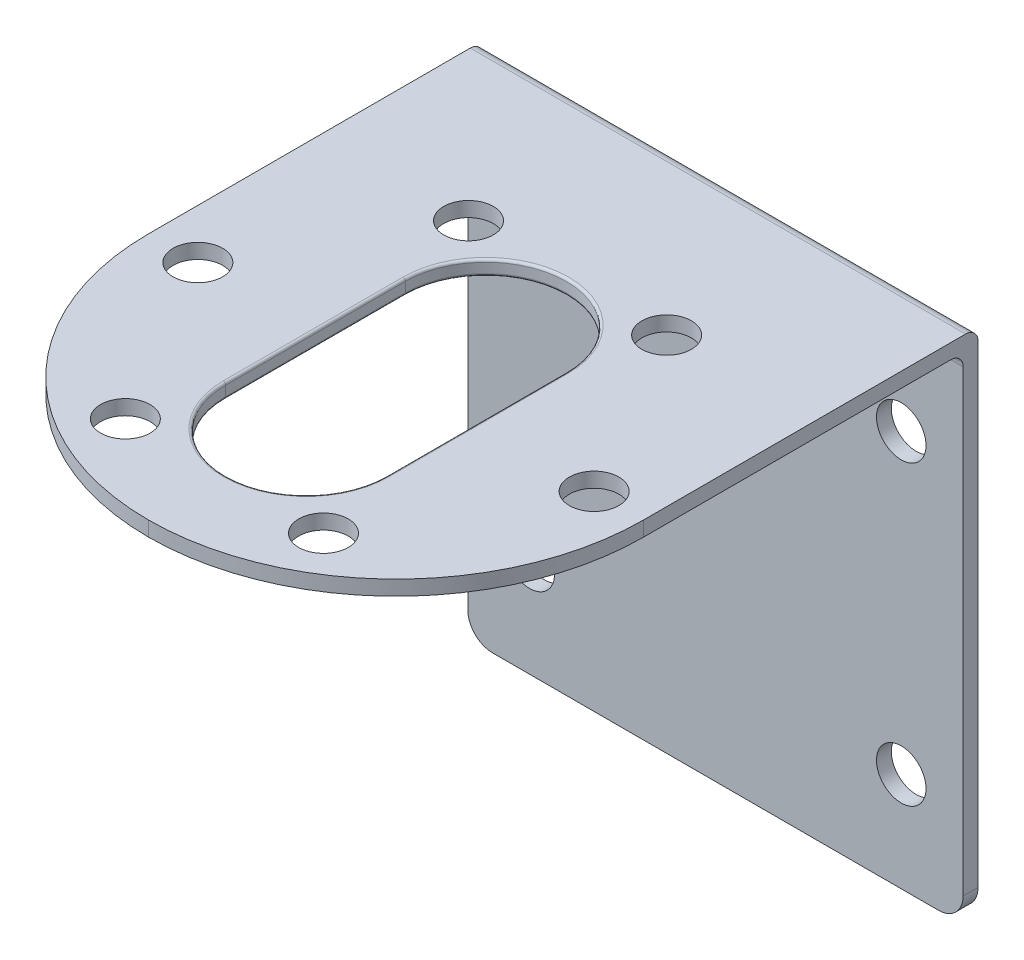
SolidWorks part; units mm, degrees
material "延性铁"
ref_plane "Front" through (0, 0, 0) normal (0, 0, 1) x (1, 0, 0)
ref_plane "Top" through (0, 0, 0) normal (0, 1, 0) x (1, 0, 0)
ref_plane "Right" through (0, 0, 0) normal (1, 0, 0) x (0, 0, -1)
sketch "草图2" plane through (0, 0, 0) normal (0, 0, 1) x (1, 0, 0)
  line L1 (0, 0) -> (40, 0)
  line L2 (0, 0) -> (0, 40)
  line L3 (0, 40) -> (40, 40)
  line L4 (40, 0) -> (40, 40)
  circle A0 centre (5, 32) radius 2
  circle A1 centre (35, 8) radius 2
  circle A2 centre (5, 8) radius 2
  circle A3 centre (35, 32) radius 2
  dimension "D3" = 5
  dimension "D4" = 8
  dimension "D5" = 5
  dimension "D6" = 8
  dimension "D1" = 40
  dimension "D2" = 40
extrude "凸台-拉伸1" add sketch "草图2" along normal blind 1.2
sketch "草图3" plane through (0, 40, 0) normal (0, 1, 0) x (1, 0, 0)
  line L1 (40, 0) -> (0, 0)
  line L2 (40, 0) -> (40, -47)
  line L3 (40, -47) -> (0, -47)
  line L4 (0, 0) -> (0, -47)
  dimension "D1" = 47
extrude "凸台-拉伸2" add sketch "草图3" along normal blind 1.2
fillet "圆角1" radius 1 2 edges at (20, 41.2, 0) (20, 40, 1.2)
fillet "圆角2" radius 20 2 edges at (0, 40.6, 47) (40, 40.6, 47)
fillet "圆角3" radius 2 2 edges at (40, 0, 0.6) (0, 0, 0.6)
sketch "草图4" plane through (0, 41.2, 0) normal (0, 1, 0) x (1, 0, 0)
  line L0 (40, -27) -> (0, -27)
  arc A0 (0, -27) -> (20, -47) centre (20, -27) ccw construction
  circle A1 centre (20, -27) radius 16
  dimension "D1" = 32
sketch "草图5" plane through (0, 41.2, 0) normal (0, 1, 0) x (1, 0, 0)
  line L0 (20, -19.75) -> (20, -34.25) construction
  line L1 (40, -27) -> (0, -27) construction
  line L2 (26.5, -19.75) -> (26.5, -34.25)
  line L3 (13.5, -19.75) -> (13.5, -34.25)
  arc A0 (26.5, -19.75) -> (13.5, -19.75) centre (20, -19.75) ccw
  arc A1 (13.5, -34.25) -> (26.5, -34.25) centre (20, -34.25) ccw
  point P4 (20, -27)
  point P9 (20, -40.75)
  point P10 (20, -13.25)
  dimension "D1" = 13
  dimension "D2" = 27.5
extrude "切除-拉伸1" cut sketch "草图5" against normal through all
sketch "草图7" plane through (0, 41.2, 0) normal (0, 1, 0) x (1, 0, 0)
  line L0 (40, -27) -> (0, -27) construction
  circle A0 centre (36, -27) radius 2
  circle A1 centre (20, -27) radius 16 construction
  circle A2 centre (4, -27) radius 2
  circle A3 centre (28, -40.8564) radius 2
  circle A4 centre (12, -40.8564) radius 2
  circle A5 centre (28, -13.1436) radius 2
  circle A6 centre (12, -13.1436) radius 2
  dimension "D1" = 60
  dimension "D2" = 60
extrude "切除-拉伸3" cut sketch "草图7" against normal through all
fillet "圆角4" radius 0.2 8 edges at (20, 41.2, 40.75) (13.5, 41.2, 27) (20, 41.2, 13.25) (20, 40, 13.25) (13.5, 40, 27) (20, 40, 40.75) (26.5, 41.2, 27) (26.5, 40, 27)
